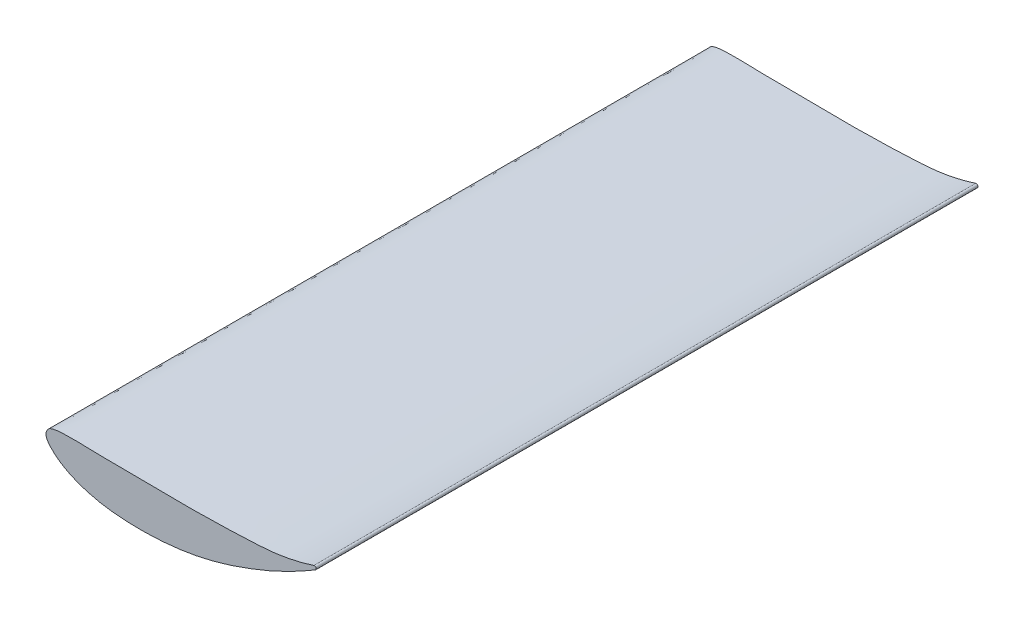
SolidWorks part; units mm, degrees
ref_plane "Front Plane" through (0, 0, 0) normal (0, 0, 1) x (1, 0, 0)
ref_plane "Top Plane" through (0, 0, 0) normal (0, 1, 0) x (1, 0, 0)
ref_plane "Right Plane" through (0, 0, 0) normal (1, 0, 0) x (0, 0, -1)
sketch "Sketch1" plane through (0, 0, 0) normal (0, 0, 1) x (1, 0, 0)
  line L0 (76.9837, 0) -> (474.4124, 45.2813) construction
  line L1 (0, 0) -> (545.4958, 0) construction
  line L2 (441.905, 24.9418) -> (474.4124, 45.2813) construction
  arc A0 (441.1212, 27.2242) -> (442.6889, 22.6594) centre (441.905, 24.9418) cw
  spline S0 degree 3 poles (441.1212, 27.2242) (439.5102, 26.6709) (426.4261, 22.546) (396.7625, 15.335) (357.2647, 12.8318) (317.0609, 11.318) (276.9474, 10.5073) (236.7066, 10.6726) (196.4668, 11.7193) (162.8843, 11.0235) (136.0529, 12.2419) (119.2558, 12.3255) (105.8571, 12.3861) (95.8161, 12.0228) (87.4842, 10.8855) (79.5903, 8.2048) (77.0847, 3.0635) (76.9837, 0) (76.831, -4.6312) (81.9434, -11.1487) (90.1004, -19.2159) (99.3347, -25.7384) (110.203, -31.5407) (124.1368, -37.3624) (141.4367, -42.4684) (168.7595, -47.3083) (202.6482, -49.2121) (242.8826, -47.4132) (282.7455, -41.7805) (322.0025, -31.6959) (360.965, -17.8201) (398.9743, -1.6424) (428.017, 13.9964) (440.7657, 21.4886) (442.6889, 22.6594) knots 0.559159 0.559159 0.559159 0.559159 0.565818 0.613605 0.661047 0.708588 0.756203 0.803924 0.851705 0.899416 0.923359 0.947241 0.959164 0.971044 0.982921 0.989132 1 1 1 1.016429 1.025764 1.041718 1.056086 1.069632 1.095356 1.120078 1.168217 1.215744 1.263211 1.311129 1.359857 1.409547 1.460672 1.469486 1.469486 1.469486 1.469486
  spline S1 degree 3 poles (474.4124, 45.2813) (474.4111, 45.2828) (474.401, 45.2894) (474.375, 45.2847) (474.3434, 45.2734) knots 0.514617 0.514617 0.514617 0.514617 0.514802 0.515655 0.515655 0.515655 0.515655
  dimension "D1" = 400
  dimension "D2" = 6.5
extrude "Boss-Extrude1" add sketch "Sketch1" along normal blind 450 and the other way blind 450 contours A0 S0 region at (234.977, -12.4703, 0)
